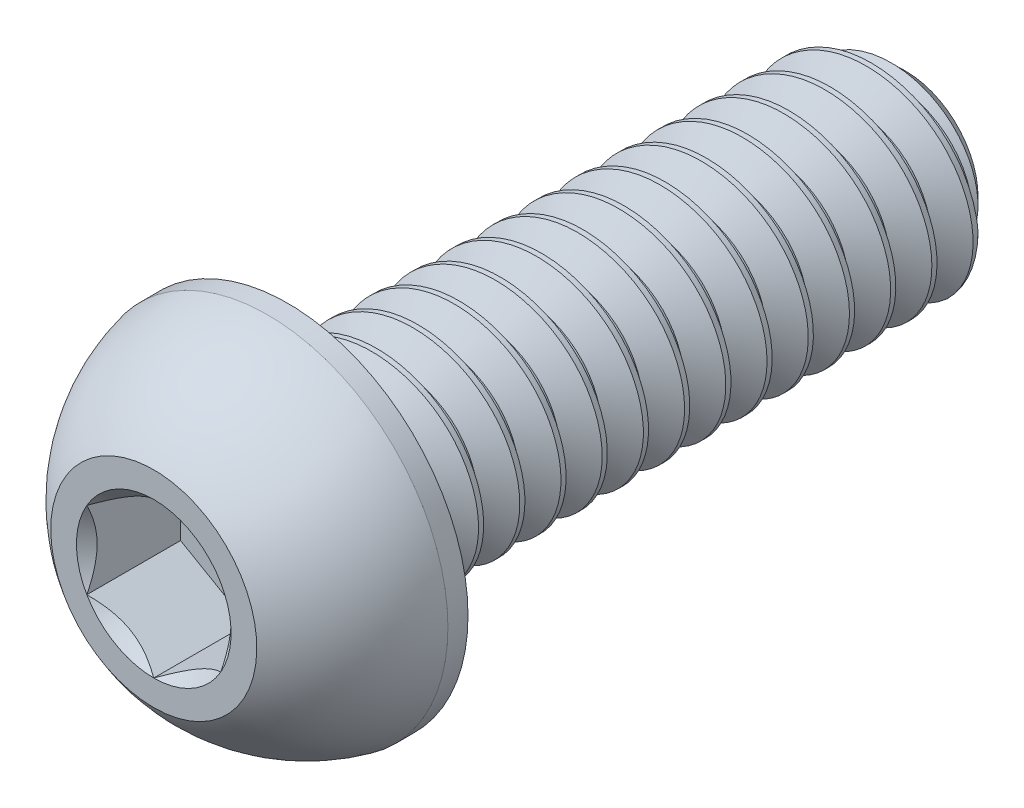
SolidWorks part; units mm, degrees
ref_plane "Front" through (0, 0, 0) normal (0, 0, 1) x (1, 0, 0)
ref_plane "Top" through (0, 0, 0) normal (0, 1, 0) x (1, 0, 0)
ref_plane "Right" through (0, 0, 0) normal (1, 0, 0) x (0, 0, -1)
sketch "Sketch1" plane through (0, 0, 0) normal (1, 0, 0) x (0, 0, -1)
  line L2 (1.3, 1) -> (7.3, 1)
  line L3 (7.3, 1) -> (7.3, 0)
  line L4 (7.3, 0) -> (1.3, 0)
  line L6 (1.105, 1.75) -> (1.3, 1.75) construction
  line L7 (7.3, 1) -> (7.3, -1) construction
  line L8 (0, 0) -> (1.3, 0) construction
  line L9 (1.3, 1.75) -> (1.3, -1.75) construction
  line L11 (1.3, 1) -> (1.3, 0)
  line L13 (0, 0.65) -> (0, -0.65) construction
  line L14 (0, 0.65) -> (0, 1) construction
  arc A3 (0, 1) -> (1.105, 1.75) centre (1.4858, 0) cw construction
  dimension "D1" = 0.195
revolve "Revolve1" add sketch "Sketch1" angle 360 mid plane about L4
sketch "Sketch3" plane through (0, 0, -7.3) normal (0, 0, -1) x (-1, 0, 0)
  circle A0 centre (0, 0) radius 1
curve "Helix/Spiral1" pitch 0.4 height 6.4 radius 1 centre (0, 0, -7.3) axis (0, 0, 1) start towards (0, 1, 0)
sketch "Sketch2" plane through (0, 0, 0) normal (1, 0, 0) x (0, 0, -1)
  line L0 (7.3, 1) -> (7.65, 1)
  line L1 (7.65, 1) -> (7.5, 0.7402)
  line L2 (7.5, 0.7402) -> (7.45, 0.7402)
  line L3 (7.45, 0.7402) -> (7.3, 1)
  line L4 (7.375, 0.8701) -> (7.575, 0.8701) construction
  dimension "D1" = 60
  dimension "D2" = 0.05
  dimension "D3" = 0.2
chamfer "Chamfer1" distance 0.3 angle 45 1 edges at (0, 1, -7.3)
sweep "Cut-Sweep1" cut profiles "Sketch2" path "Helix/Spiral1" align with end faces yes
sketch "Sketch7" plane through (0, 0, 0) normal (1, 0, 0) x (0, 0, -1)
  line L6 (1.105, 1.75) -> (1.3, 1.75) construction
  line L8 (0, 0) -> (1.3, 0) construction
  line L11 (1.3, 1.75) -> (1.3, -1.75) construction
  line L12 (1.105, 1.75) -> (1.3, 1.75)
  line L13 (0, 0) -> (1.3, 0)
  line L14 (0, 0.65) -> (0, -0.65) construction
  line L15 (1.3, 1.75) -> (1.3, 0)
  line L16 (0, 1) -> (0, 0)
  arc A2 (1.105, 1.75) -> (0, 1) centre (1.4858, 0) ccw construction
  arc A3 (1.105, 1.75) -> (0, 1) centre (1.4858, 0) ccw
revolve "Revolve2" add sketch "Sketch7" angle 360 mid plane about L13
sketch "Sketch5" plane through (0, 0, 0) normal (0, 0, 1) x (1, 0, 0)
  line L1 (0.65, -0.3753) -> (0.65, 0.3753)
  line L2 (0.65, 0.3753) -> (0, 0.7506)
  line L3 (0, 0.7506) -> (-0.65, 0.3753)
  line L4 (-0.65, 0.3753) -> (-0.65, -0.3753)
  line L5 (-0.65, -0.3753) -> (0, -0.7506)
  line L6 (0, -0.7506) -> (0.65, -0.3753)
  circle A0 centre (0, 0) radius 0.65 construction
extrude "Cut-Extrude2" cut sketch "Sketch5" against normal blind 0.91
sketch "Sketch6" plane through (0, 0, 0) normal (0, 0, 1) x (1, 0, 0)
  circle A0 centre (0, 0) radius 0.7506
extrude "Cut-Extrude3" cut sketch "Sketch6" against normal blind 0.91 draft 45
sketch "Sketch9" [suppressed] plane through (0, 0, -4.2164) normal (0, 0, 1) x (1, 0, 0)
  circle A2 centre (0, 0) radius 3.9687
extrude "Boss-Extrude2" [suppressed] add sketch "Sketch9" against normal offset from surface (9.525 mm away) 28.575 up to face at (0, 0.7, -7.3)
sketch "Sketch10" plane through (0, 0, 0) normal (1, 0, 0) x (0, 0, -1)
  line L0 (7.3, 1) -> (7.3, -1) construction
  point P0 (6.7, -1)
  dimension "D1" = 0.6
equation "\"D3@Helix/Spiral1\" = \"Lg@Sketch1\" + \"D4@Helix/Spiral1\""
equation "\"D2@Sketch2\" = \"D4@Helix/Spiral1\" * .125"
equation "\"D3@Sketch2\" = \"D4@Helix/Spiral1\" * .5"
equation "\"D1@Chamfer1\" = \"D4@Helix/Spiral1\" * .75"
equation "\"D1@Cut-Extrude2\" = \"Head Ht@Sketch1\" * .7"
equation "\"D1@Sketch1\" = \"Head Ht@Sketch1\" * .15"
equation "\"D1@Sketch10\" = \"D4@Helix/Spiral1\" * 1.5"
equation "\"D1@Cut-Extrude3\" = \"D1@Cut-Extrude2\""
